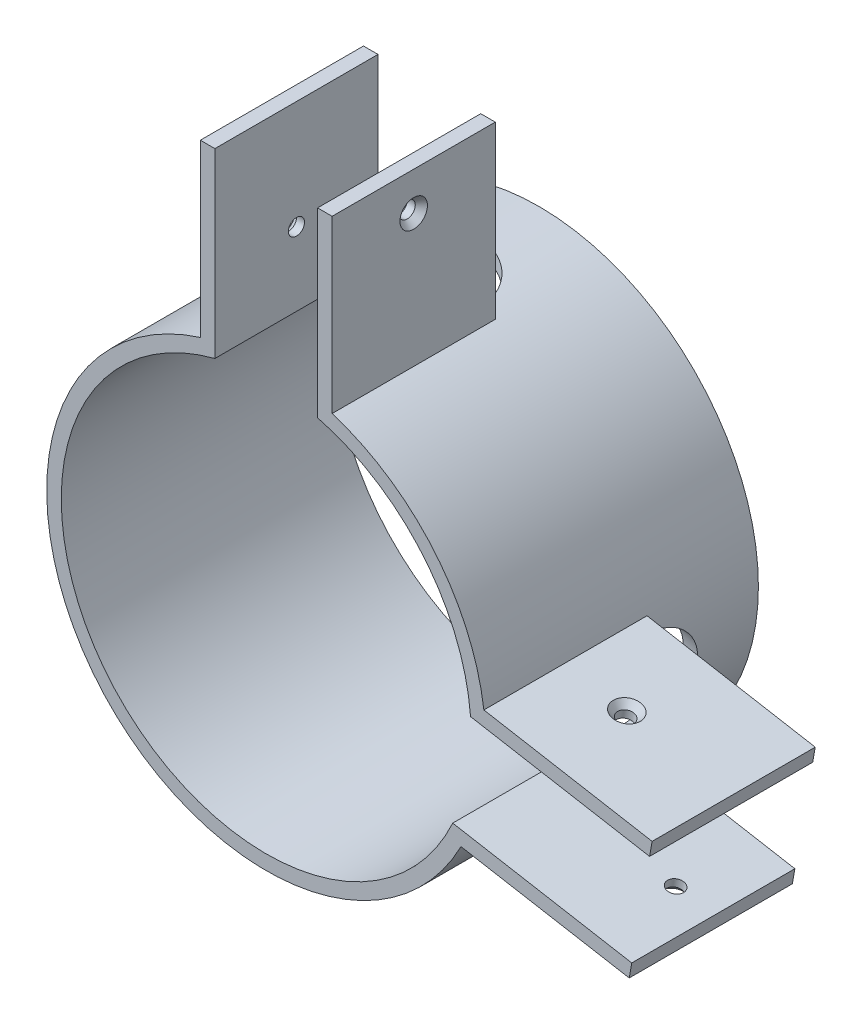
SolidWorks part; units mm, degrees
ref_plane "Plan de face" through (0, 0, 0) normal (0, 0, 1) x (1, 0, 0)
ref_plane "Plan de dessus" through (0, 0, 0) normal (0, 1, 0) x (1, 0, 0)
ref_plane "Plan de droite" through (0, 0, 0) normal (1, 0, 0) x (0, 0, -1)
sketch "Esquisse1" plane through (0, 0, 0) normal (0, 0, 1) x (1, 0, 0)
  line L0 (0, 0) -> (0, 24.15) construction
  line L1 (0, 0) -> (22.2074, -3.9158) construction
  circle A0 centre (0, 0) radius 22.55
  circle A1 centre (0, 0) radius 24.15
  dimension "D1" = 45.1
  dimension "D3" = 100
  dimension "D2" = 1.6
extrude "Boss.-Extru.1" add sketch "Esquisse1" along normal blind 30
sketch "Esquisse2" plane through (0, 0, 0) normal (0, 1, 0) x (1, 0, 0)
  line L1 (-24.15, -30) -> (24.15, -30) construction
  line L2 (-5.65, -30) -> (-5.65, -12.0501)
  line L3 (5.65, -12.0501) -> (5.65, -30)
  line L6 (-5.65, -30) -> (5.65, -30)
  arc A0 (-5.65, -12.0501) -> (5.65, -12.0501) centre (0, -12.0501) cw
  dimension "D1" = 11.3
extrude "Enlèv. mat.-Extru.1" cut sketch "Esquisse2" along normal through all
sketch "Esquisse3" plane through (-5.65, 0, 0) normal (1, 0, 0) x (0, 0, -1)
  line L0 (-12.0501, 21.8307) -> (-30, 21.8307)
  line L1 (-12.0501, 21.8307) -> (-12.0501, 41.8307)
  line L2 (-30, 21.8307) -> (-30, 41.8307)
  line L3 (-12.0501, 41.8307) -> (-30, 41.8307)
  dimension "D1" = 20
extrude "Boss.-Extru.2" add sketch "Esquisse3" against normal blind 1.6
sketch "Esquisse4" plane through (5.65, 0, 0) normal (-1, 0, 0) x (0, 0, 1)
  line L0 (30, 21.8307) -> (12.0501, 21.8307)
  line L1 (30, 21.8307) -> (30, 41.8307)
  line L2 (12.0501, 21.8307) -> (12.0501, 41.8307)
  line L3 (30, 41.8307) -> (12.0501, 41.8307)
  dimension "D1" = 20
extrude "Boss.-Extru.3" add sketch "Esquisse4" against normal blind 1.6
hole_wizard "Fraisage pour vis à tête fraisée bombée #01" positions "Esquisse5" profile "Esquisse6" countersink size "#0" standard "Ansi Inch" end condition up to next
sketch "Esquisse5" plane through (7.25, 0, 0) normal (1, 0, 0) x (0, 0, -1)
  point P0 (-21.0251, 37.6189)
sketch "Esquisse6" plane through (7.25, 37.6189, 21.0251) normal (0, 1, 0) x (0, 0, -1)
  line L0 (0, 0) -> (0, 1.6)
  line L1 (0, 1.6) -> (0.889, 1.6)
  line L2 (0.889, 1.6) -> (0.889, 0.7159)
  line L3 (0.889, 0.7159) -> (1.5113, 0)
  line L5 (1.5113, 0) -> (0, 0)
  line L6 (-0.889, 0.7159) -> (-1.5113, 0) construction
  line L11 (0, -6.35) -> (0, 107.95) construction
  dimension "Diamètre du perçage jusqu'au prochain" = 1.778
  dimension "Profondeur du perçage jusqu'au prochain" = 1.6
  dimension "Diamètre du fraisage entrant" = 3.0226
  dimension "Angle du fraisage entrant" = 82
hole_wizard "Fraisage pour vis à tête fraisée bombée #02" positions "Esquisse7" profile "Esquisse8" countersink size "#0" standard "Ansi Inch" end condition up to next
sketch "Esquisse7" plane through (-7.25, 0, 0) normal (-1, 0, 0) x (0, 0, 1)
  point P0 (21.0251, 29.8931)
sketch "Esquisse8" plane through (-7.25, 29.8931, 21.0251) normal (0, 1, 0) x (0, 0, 1)
  line L0 (0, 0) -> (0, 1.6)
  line L1 (0, 1.6) -> (0.889, 1.6)
  line L2 (0.889, 1.6) -> (0.889, 0.7159)
  line L3 (0.889, 0.7159) -> (1.5113, 0)
  line L5 (1.5113, 0) -> (0, 0)
  line L6 (-0.889, 0.7159) -> (-1.5113, 0) construction
  line L11 (0, -6.35) -> (0, 107.95) construction
  dimension "Diamètre du perçage jusqu'au prochain" = 1.778
  dimension "Profondeur du perçage jusqu'au prochain" = 1.6
  dimension "Diamètre du fraisage entrant" = 3.0226
  dimension "Angle du fraisage entrant" = 82
pattern_circular "Répétition circulaire1" count 2 over 100 about axis through (0, 0, 0) along (0, 0, 1) of "Enlèv. mat.-Extru.1", "Boss.-Extru.2", "Boss.-Extru.3", "Fraisage pour vis à tête fraisée bombée #01", "Fraisage pour vis à tête fraisée bombée #02" reverse direction yes
